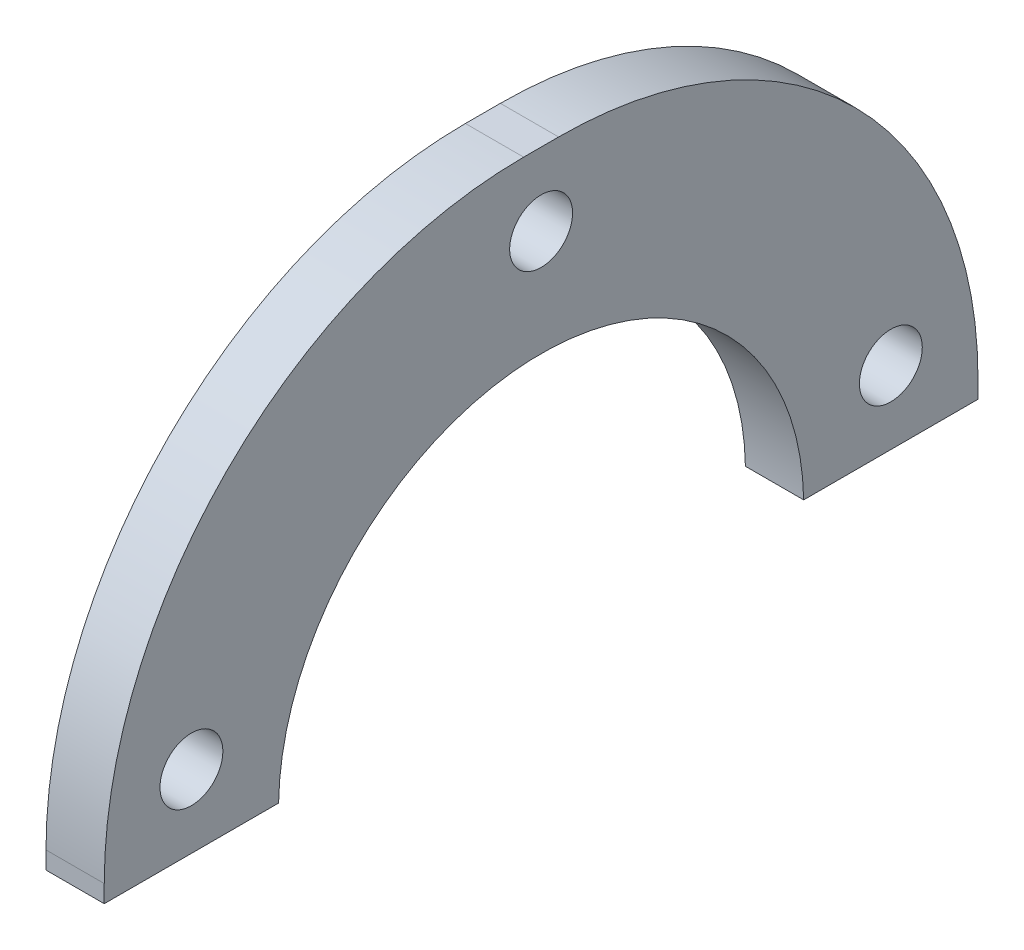
SolidWorks part; units mm, degrees
material "6061 Alloy"
ref_plane "Front Plane" through (0, 0, 0) normal (0, 0, 1) x (1, 0, 0)
ref_plane "Top Plane" through (0, 0, 0) normal (0, 1, 0) x (1, 0, 0)
ref_plane "Right Plane" through (0, 0, 0) normal (1, 0, 0) x (0, 0, -1)
sketch "Sketch1" plane through (0, 0, 0) normal (1, 0, 0) x (0, 0, -1)
  line L4 (0, 12.7) -> (0, 4.6747) construction
  line L5 (-23.8125, -11.9063) -> (23.8125, -11.9062)
  line L6 (-23.8125, -11.9063) -> (-23.8125, 11.9062)
  line L7 (23.8125, 11.9063) -> (-23.8125, 11.9062)
  line L8 (23.8125, -11.9062) -> (23.8125, 11.9063)
  line L9 (-23.8125, -11.9063) -> (23.8125, 11.9063) construction
  line L10 (-23.8125, 11.9062) -> (23.8125, -11.9062) construction
  circle A2 centre (0, -12.1603) radius 15.5575 construction
  circle A3 centre (0, 7.7851) radius 3.3274 construction
  circle A4 centre (19.6914, -7.7851) radius 3.3274 construction
  circle A5 centre (-19.6913, -7.7851) radius 3.3274 construction
  point P0 (0, 0)
  dimension "D6" = 31.115
  dimension "D7" = 6.6548
  dimension "D8" = 0.7937
  dimension "D10" = 0.7937
  dimension "D11" = 0.7937
  dimension "D12" = 1.2866
  dimension "D13" = 1.0604
  dimension "D9" = 0.7937
  dimension "D1" = 23.8125
  dimension "D2" = 0.254
  dimension "D5" = 47.625
extrude "Boss-Extrude1" add sketch "Sketch1" along normal blind 3.175
sketch "Sketch2" plane through (3.175, 0, 0) normal (1, 0, 0) x (0, 0, -1)
  line L1 (-23.8125, -11.9063) -> (23.8125, -11.9062) construction
  circle A0 centre (0, -12.1603) radius 14.3129
  point P2 (0, -12.1603)
  dimension "D1" = 28.6258
  dimension "D2" = 0.254
extrude "Cut-Extrude1" cut sketch "Sketch2" against normal through all
hole_wizard "1/8 (0.135) Diameter Hole1" positions "Sketch3" profile "Sketch4" hole size "1/8" standard "ANSI Inch"
sketch "Sketch3" plane through (3.175, 0, 0) normal (1, 0, 0) x (0, 0, -1)
  line L0 (-23.8125, -11.9063) -> (-14.3106, -11.9063) construction
  line L1 (23.8125, 11.9063) -> (-23.8125, 11.9062) construction
  line L2 (14.3106, -11.9062) -> (23.8125, -11.9062) construction
  circle A0 centre (0, 7.9375) radius 3.175 construction
  circle A1 centre (-19.0616, -7.9375) radius 3.175 construction
  circle A2 centre (19.0616, -7.9375) radius 3.175 construction
  point P0 (-19.0616, -7.9375)
  point P2 (0, 7.9375)
  point P4 (19.0616, -7.9375)
  point P12 (0, 11.9062)
  point P13 (-19.0616, -11.9063)
  point P16 (19.0616, -11.9063)
  dimension "D3" = 6.35
  dimension "D2" = 0.7937
  dimension "D1" = 0.7937
sketch "Sketch4" plane through (3.175, -7.9375, 19.0616) normal (0, 1, 0) x (0, 0, -1)
  line L0 (0, 0) -> (0, 20.0322)
  line L1 (0, 20.0322) -> (1.7145, 19.002)
  line L2 (1.7145, 19.002) -> (1.7145, 0)
  line L5 (1.7145, 0) -> (0, 0)
  line L10 (0, 20.0322) -> (-1.7145, 19.002) construction
  line L11 (0, -6.35) -> (0, 107.95) construction
  dimension "Hole Dia." = 3.429
  dimension "Hole Depth" = 19.002
  dimension "Drill Angle" = 118
fillet "Fillet1" radius 22.86 2 edges at (1.5875, 11.9063, -23.8125) (1.5875, 11.9062, 23.8125)
